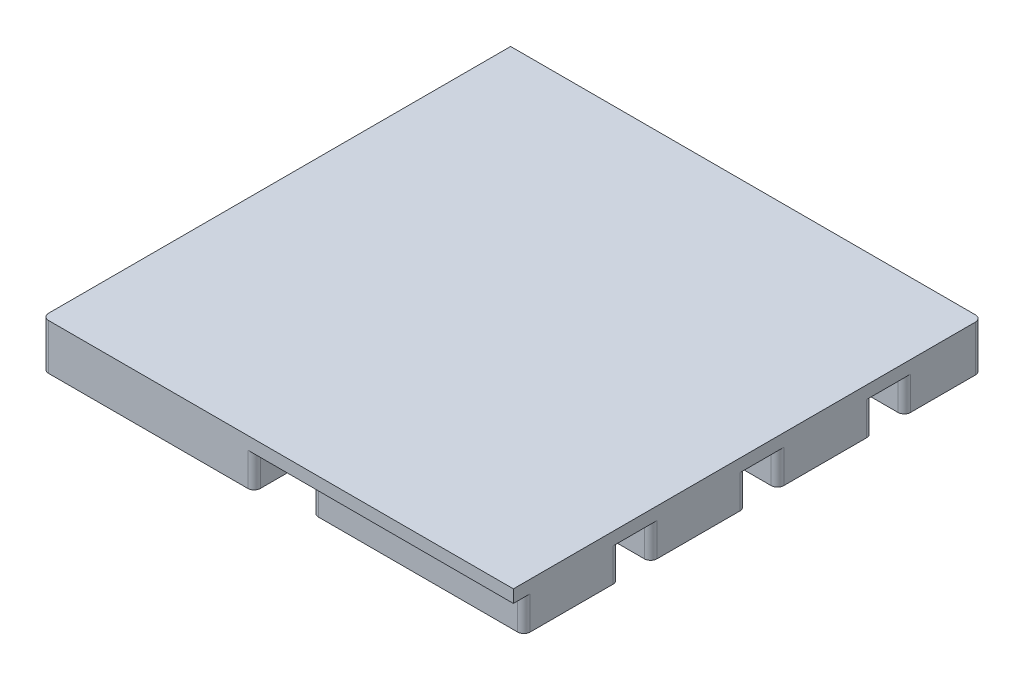
SolidWorks part; units mm, degrees
ref_plane "Front Plane" through (0, 0, 0) normal (0, 0, 1) x (1, 0, 0)
ref_plane "Top Plane" through (0, 0, 0) normal (0, 1, 0) x (1, 0, 0)
ref_plane "Right Plane" through (0, 0, 0) normal (1, 0, 0) x (0, 0, -1)
sketch "Sketch2" plane through (0, 0, 0) normal (0, 1, 0) x (1, 0, 0)
  line L1 (0, 0) -> (149, 0)
  line L2 (0, 0) -> (0, 148.13)
  line L3 (0, 148.13) -> (149, 148.13)
  line L4 (149, 0) -> (149, 148.13)
  dimension "D1" = 149
  dimension "D2" = 148.13
extrude "Boss-Extrude1" add sketch "Sketch2" along normal blind 4
sketch "Sketch3" plane through (0, 4, 0) normal (0, 1, 0) x (1, 0, 0)
  line L0 (0, 148.13) -> (0, 0) construction
  line L1 (149, 148.13) -> (82, 148.13)
  line L2 (149, 148.13) -> (149, 123.63)
  line L3 (149, 123.63) -> (82, 123.63)
  line L4 (82, 148.13) -> (82, 123.63)
  line L5 (0, 144.7967) -> (67, 144.7967)
  line L6 (0, 144.7967) -> (0, 120.2967)
  line L7 (0, 120.2967) -> (67, 120.2967)
  line L8 (67, 144.7967) -> (67, 120.2967)
  line L9 (149, 148.13) -> (0, 148.13) construction
  line L10 (149, 0) -> (149, 148.13) construction
  line L11 (149, 113.73) -> (82, 113.73)
  line L12 (149, 113.73) -> (149, 83.53)
  line L13 (149, 83.53) -> (82, 83.53)
  line L14 (82, 113.73) -> (82, 83.53)
  line L15 (97, 113.73) -> (97, 101.73) construction
  line L16 (0, 110.3967) -> (67, 110.3967)
  line L17 (0, 110.3967) -> (0, 80.1967)
  line L18 (0, 80.1967) -> (67, 80.1967)
  line L19 (67, 110.3967) -> (67, 80.1967)
  line L20 (149, 73.63) -> (82, 73.63)
  line L21 (149, 73.63) -> (149, 43.43)
  line L22 (149, 43.43) -> (82, 43.43)
  line L23 (82, 73.63) -> (82, 43.43)
  line L24 (0, 70.2967) -> (67, 70.2967)
  line L25 (0, 70.2967) -> (0, 40.0967)
  line L26 (0, 40.0967) -> (67, 40.0967)
  line L27 (67, 70.2967) -> (67, 40.0967)
  line L28 (0, 30.1967) -> (67, 30.1967)
  line L29 (0, 30.1967) -> (0, -0.0033)
  line L30 (0, -0.0033) -> (67, -0.0033)
  line L31 (67, 30.1967) -> (67, -0.0033)
  line L32 (97, 101.73) -> (97, 94.53) construction
  line L33 (149, 33.53) -> (82, 33.53)
  line L34 (149, 33.53) -> (149, 3.33)
  line L35 (149, 3.33) -> (82, 3.33)
  line L36 (82, 33.53) -> (82, 3.33)
  line L37 (13, 144.7967) -> (13, 137.9467) construction
  line L38 (13, 137.9467) -> (41, 137.9467)
  line L39 (13, 137.9467) -> (13, 131.9467) construction
  line L40 (13, 131.9467) -> (13, 120.2967) construction
  line L41 (13, 131.9467) -> (41, 131.9467)
  line L42 (97, 148.13) -> (97, 140.63) construction
  line L43 (97, 140.63) -> (97, 134.63) construction
  line L44 (97, 134.63) -> (97, 123.63) construction
  line L45 (97, 140.63) -> (125, 140.63)
  line L46 (97, 134.63) -> (125, 134.63)
  line L47 (0, 0) -> (149, 0) construction
  line L48 (97, 94.53) -> (97, 83.53) construction
  line L49 (97, 101.73) -> (125, 101.73)
  line L50 (97, 94.53) -> (125, 94.53)
  line L51 (13, 110.3967) -> (13, 98.3967) construction
  line L52 (13, 98.3967) -> (13, 91.1967) construction
  line L53 (13, 91.1967) -> (13, 80.1967) construction
  line L54 (13, 98.3967) -> (41, 98.3967)
  line L55 (13, 91.1967) -> (40.3, 91.1967)
  line L56 (13, 70.2967) -> (13, 58.2967) construction
  line L57 (13, 58.2967) -> (13, 51.0967) construction
  line L58 (13, 51.0967) -> (13, 40.0967) construction
  line L59 (13, 58.2967) -> (41, 58.2967)
  line L60 (13, 51.0967) -> (40.3, 51.0967)
  line L61 (97, 73.63) -> (97, 61.63) construction
  line L62 (97, 61.63) -> (97, 54.43) construction
  line L63 (97, 54.43) -> (97, 43.43) construction
  line L64 (97, 61.63) -> (125, 61.63)
  line L65 (97, 54.43) -> (124.3, 54.43)
  line L66 (13, 30.1967) -> (13, 18.1967) construction
  line L67 (13, 18.1967) -> (13, 10.9967) construction
  line L68 (13, 10.9967) -> (13, -0.0033) construction
  line L69 (13, 18.1967) -> (41, 18.1967)
  line L70 (13, 10.9967) -> (40.3, 10.9967)
  line L71 (97, 33.53) -> (97, 21.53) construction
  line L72 (97, 21.53) -> (97, 14.33) construction
  line L73 (97, 14.33) -> (97, 3.33) construction
  line L74 (97, 21.53) -> (125, 21.53)
  line L75 (97, 14.33) -> (124.3, 14.33)
  arc A0 (13, 131.9467) -> (13, 137.9467) centre (13, 134.9467) cw
  arc A2 (41, 137.9467) -> (41, 131.9467) centre (41, 134.9467) cw
  arc A3 (97, 134.63) -> (97, 140.63) centre (97, 137.63) cw
  arc A4 (125, 140.63) -> (125, 134.63) centre (125, 137.63) cw
  arc A5 (97, 94.53) -> (97, 101.73) centre (97, 98.13) cw
  arc A6 (125, 101.73) -> (125, 94.53) centre (125, 98.13) cw
  arc A7 (13, 91.1967) -> (13, 98.3967) centre (13, 94.7967) cw
  arc A9 (40.3, 91.1967) -> (41, 98.3967) centre (40.3, 94.8307) ccw
  arc A10 (13, 51.0967) -> (13, 58.2967) centre (13, 54.6967) cw
  arc A11 (41, 58.2967) -> (40.3, 51.0967) centre (40.3, 54.7307) cw
  arc A12 (97, 54.43) -> (97, 61.63) centre (97, 58.03) cw
  arc A13 (125, 61.63) -> (124.3, 54.43) centre (124.3, 58.064) cw
  arc A14 (13, 10.9967) -> (13, 18.1967) centre (13, 14.5967) cw
  arc A15 (41, 18.1967) -> (40.3, 10.9967) centre (40.3, 14.6307) cw
  arc A16 (97, 14.33) -> (97, 21.53) centre (97, 17.93) cw
  arc A17 (125, 21.53) -> (124.3, 14.33) centre (124.3, 17.964) cw
  line M24 (0, 148.13) -> (0, 0)
  line M25 (0, 0) -> (149, 0)
  line M26 (149, 0) -> (149, 148.13)
  line M27 (149, 148.13) -> (0, 148.13)
  dimension "D31" = 24
  dimension "D1" = 67
  dimension "D2" = 24.5
  dimension "D3" = 3.3333
  dimension "D4" = 67
  dimension "D5" = 24.5
  dimension "D6" = 9.9
  dimension "D7" = 30.2
  dimension "D8" = 67
  dimension "D9" = 30.2
  dimension "D10" = 9.9
  dimension "D11" = 67
  dimension "D12" = 9.9
  dimension "D13" = 30.2
  dimension "D14" = 67
  dimension "D15" = 9.9
  dimension "D16" = 30.2
  dimension "D17" = 67
  dimension "D18" = 30.2
  dimension "D19" = 9.9
  dimension "D20" = 67
  dimension "D21" = 9.9
  dimension "D22" = 30.2
  dimension "D23" = 67
  dimension "D24" = 6.85
  dimension "D25" = 6
  dimension "D26" = 28
  dimension "D27" = 13
  dimension "D28" = 7.5
  dimension "D29" = 6
  dimension "D30" = 28
  dimension "D32" = 12
  dimension "D33" = 11
  dimension "D34" = 28
  dimension "D35" = 12
  dimension "D36" = 11
  dimension "D37" = 28
  dimension "D38" = 12
  dimension "D39" = 11
  dimension "D40" = 12
  dimension "D41" = 11
  dimension "D42" = 12
  dimension "D43" = 11
  dimension "D44" = 12
  dimension "D45" = 11
  dimension "D46" = 28
  dimension "D47" = 28
  dimension "D48" = 28
  dimension "D49" = 28
extrude "Boss-Extrude3" add sketch "Sketch3" against normal blind 14.5 contours L8 L5 L7 L38 A2 L41 A0 M24 | L4 L3 L45 A4 L46 A3 M27 M26 | L19 L16 L18 A9 L55 A7 L54 M24 | L11 L14 L13 L49 A6 L50 A5 M26 | L27 L24 L26 L59 A11 L60 A10 M24 | L20 L23 L22 L64 A13 L65 A12 M26 | L31 L28 L69 A15 L70 A14 M24 M25 | L33 L36 L35 L74 A17 L75 A16 M26 region at (148.2866, 4, -135.88) region at (148.2651, 4, -98.63) region at (33.5, 4, -144.0833) region at (148.2651, 4, -58.53) region at (33.5, 4, -109.6618) region at (148.2651, 4, -18.43) region at (33.5, 4, -69.5618) region at (33.5, 4, -29.4618)
fillet "Fillet1" radius 2 32 edges at (149, -5.25, -3.33) (149, -5.25, -33.53) (82, -5.25, -33.53) (82, -5.25, -3.33) (67, -5.25, 0) (0, -3.25, 0) (0, -5.25, -30.1967) (67, -5.25, -30.1967) (67, -5.25, -40.0967) (0, -5.25, -40.0967) (149, -5.25, -43.43) (82, -5.25, -43.43) (82, -5.25, -73.63) (67, -5.25, -70.2967) (0, -5.25, -70.2967) (0, -5.25, -80.1967) (82, -5.25, -83.53) (67, -5.25, -80.1967) (0, -5.25, -110.3967) (149, -5.25, -83.53) (149, -5.25, -73.63) (149, -5.25, -113.73) (67, -5.25, -110.3967) (82, -5.25, -113.73) (0, -5.25, -120.2967) (67, -5.25, -120.2967) (67, -5.25, -144.7967) (0, -5.25, -144.7967) (82, -5.25, -123.63) (149, -5.25, -123.63) (149, -3.25, -148.13) (82, -5.25, -148.13)
